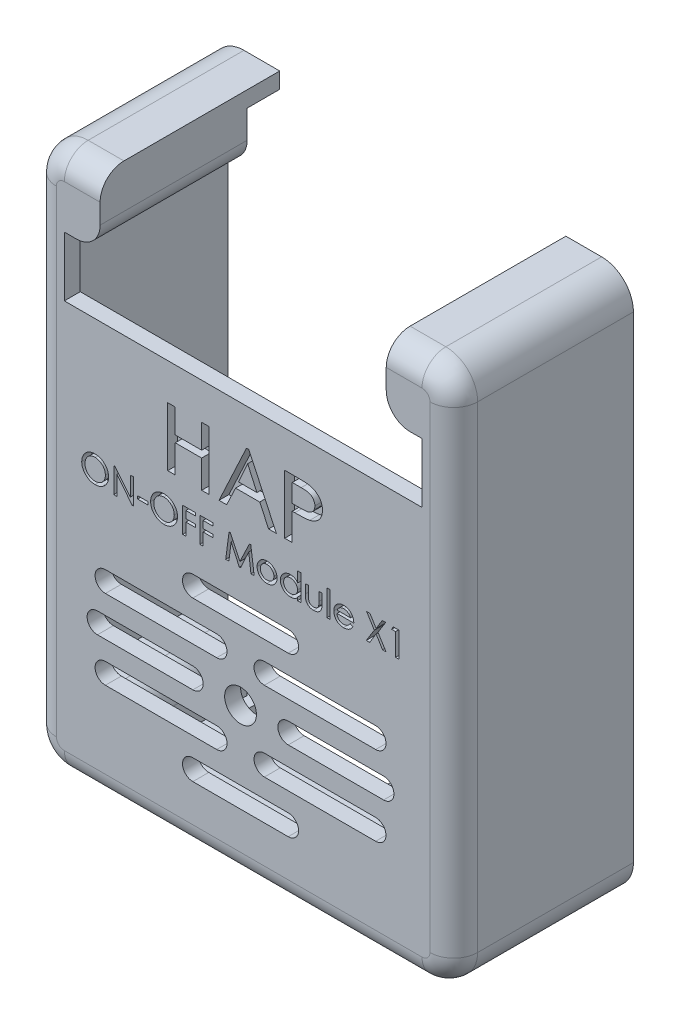
SolidWorks part; units mm, degrees
material "ABS"
ref_plane "Plano frontal" through (0, 0, 0) normal (0, 0, 1) x (1, 0, 0)
ref_plane "Plano superior" through (0, 0, 0) normal (0, 1, 0) x (1, 0, 0)
ref_plane "Plano direito" through (0, 0, 0) normal (1, 0, 0) x (0, 0, -1)
sketch "Esboço1" plane through (0, 0, 0) normal (0, 0, 1) x (1, 0, 0)
  line L1 (-26.5, -34) -> (26.5, -34)
  line L2 (-26.5, -34) -> (-26.5, 34)
  line L3 (-26.5, 34) -> (26.5, 34)
  line L4 (26.5, -34) -> (26.5, 34)
  point P0 (0, 0)
  point P6 (0, 34)
  point P7 (26.5, 0)
  dimension "D1" = 53
  dimension "D2" = 68
  dimension "D3" = 0
  dimension "D4" = 0
extrude "Ressalto-extrusão1" add sketch "Esboço1" along normal blind 22.6
fillet "Filete1" radius 4 4 edges at (-26.5, -34, 11.3) (26.5, -34, 11.3) (-26.5, 34, 11.3) (26.5, 34, 11.3)
fillet "Filete2" radius 3 8 edges at (0, 34, 22.6) (26.5, 0, 22.6) (25.3284, -32.8284, 22.6) (0, -34, 22.6) (-25.3284, -32.8284, 22.6) (-26.5, 0, 22.6) (-25.3284, 32.8284, 22.6) (25.3284, 32.8284, 22.6)
shell "Casca1" thickness 2 removed face at (0, 0, 0)
sketch "Esboço3" plane through (0, 0, 20.6) normal (0, 0, -1) x (-1, 0, 0)
  line L0 (0, 0) -> (0, -34) construction
  line L1 (22.5, -34) -> (-22.5, -34) construction
  line L2 (0, 0) -> (26.5, 0) construction
  line L3 (26.5, 30) -> (26.5, -30) construction
  line L4 (-18, -28.5) -> (-18, -32)
  line L5 (-22.5, -32) -> (22.5, -32) construction
  line L6 (-21, -25.5) -> (-24.5, -25.5)
  line L7 (-24.5, 30) -> (-24.5, -30) construction
  line L8 (-24.5, -30) -> (-24.5, -25.5)
  line L9 (-22.5, -32) -> (-18, -32)
  line L10 (22.5, -32) -> (18, -32)
  line L11 (24.5, -30) -> (24.5, -25.5)
  line L12 (21, -25.5) -> (24.5, -25.5)
  line L13 (18, -28.5) -> (18, -32)
  line L14 (18, 28.5) -> (18, 32)
  line L15 (21, 25.5) -> (24.5, 25.5)
  line L16 (24.5, 30) -> (24.5, 25.5)
  line L17 (22.5, 32) -> (18, 32)
  line L18 (-22.5, 32) -> (-18, 32)
  line L19 (-24.5, 30) -> (-24.5, 25.5)
  line L20 (-21, 25.5) -> (-24.5, 25.5)
  line L21 (-18, 28.5) -> (-18, 32)
  arc A0 (-18, -28.5) -> (-21, -25.5) centre (-21, -28.5) ccw
  arc A4 (-24.5, -30) -> (-22.5, -32) centre (-22.5, -30) ccw
  arc A5 (24.5, -30) -> (22.5, -32) centre (22.5, -30) cw
  arc A6 (18, -28.5) -> (21, -25.5) centre (21, -28.5) cw
  arc A7 (18, 28.5) -> (21, 25.5) centre (21, 28.5) ccw
  arc A8 (24.5, 30) -> (22.5, 32) centre (22.5, 30) ccw
  arc A9 (-24.5, 30) -> (-22.5, 32) centre (-22.5, 30) cw
  arc A10 (-18, 28.5) -> (-21, 25.5) centre (-21, 28.5) cw
  dimension "D1" = 21
  dimension "D2" = 28.5
  dimension "D3" = 6
extrude "Ressalto-extrusão2" add sketch "Esboço3" along normal blind 16.5
sketch "Esboço4" plane through (0, 0, 4.1) normal (0, 0, -1) x (-1, 0, 0)
  line L0 (0, -34) -> (0, 34) construction
  line L1 (22.5, -34) -> (-22.5, -34) construction
  line L2 (-22.5, 34) -> (22.5, 34) construction
  line L3 (-26.5, 0) -> (26.5, 0) construction
  line L4 (-26.5, -30) -> (-26.5, 30) construction
  line L5 (26.5, 30) -> (26.5, -30) construction
  circle A0 centre (-21, -28.5) radius 1
  circle A2 centre (21, -28.5) radius 1
  circle A3 centre (-21, 28.5) radius 1
  circle A4 centre (21, 28.5) radius 1
  dimension "D1" = 2
extrude "Corte-extrusão1" cut sketch "Esboço4" against normal blind 6
sketch "Esboço5" plane through (0, 0, 22.6) normal (0, 0, 1) x (1, 0, 0)
  line L0 (-22.5, 34) -> (22.5, 34) construction
  line L1 (-18, 34) -> (18, 34)
  line L2 (-18, 34) -> (-18, 28.5)
  line L3 (-22.5, 18) -> (22.5, 18)
  line L4 (18, 34) -> (18, 28.5)
  line L5 (21, 25.5) -> (22.5, 25.5)
  line L8 (22.5, 25.5) -> (22.5, 18)
  line L9 (0, 34) -> (0, 0) construction
  line L10 (-22.5, 25.5) -> (-22.5, 18)
  line L11 (-21, 25.5) -> (-22.5, 25.5)
  arc A0 (18, 28.5) -> (21, 25.5) centre (21, 28.5) ccw
  arc A1 (-18, 28.5) -> (-21, 25.5) centre (-21, 28.5) cw
  dimension "D1" = 18
  dimension "D2" = 18
  dimension "D4" = 22.5
extrude "Corte-extrusão2" cut sketch "Esboço5" against normal through all
sketch "Esboço6" plane through (0, 0, 0) normal (0, 0, -1) x (-1, 0, 0)
  line L5 (-18, -32) -> (18, -32) construction
  line L6 (-0.5, -32) -> (16.5, -32)
  line L7 (-0.5, -32) -> (-0.5, -34)
  line L8 (-0.5, -34) -> (16.5, -34)
  line L9 (16.5, -32) -> (16.5, -34)
  line L10 (22.5, -34) -> (-22.5, -34) construction
  line L11 (26.5, 30) -> (26.5, -30) construction
  dimension "D1" = 10
  dimension "D2" = 17
extrude "Corte-extrusão3" cut sketch "Esboço6" against normal blind 6
sketch "Esboço7" plane through (0, -34, 0) normal (0, -1, 0) x (1, 0, 0)
  line L0 (-16.5, 0) -> (-18.5, 0)
  line L1 (-22.5, 0) -> (-16.5, 0) construction
  line L2 (-18.5, 0) -> (-18.5, 8)
  line L3 (-18.5, 8) -> (2.5, 8)
  line L4 (2.5, 8) -> (2.5, 0)
  line L5 (0.5, 0) -> (22.5, 0) construction
  line L6 (2.5, 0) -> (0.5, 0)
  line L7 (0.5, 0) -> (0.5, 6)
  line L8 (0.5, 6) -> (-16.5, 6)
  line L9 (-16.5, 6) -> (-16.5, 0)
  dimension "D1" = 2
  dimension "D2" = 2
  dimension "D3" = 2
extrude "Ressalto-extrusão3" add sketch "Esboço7" along normal blind 4.5
sketch "Esboço8" plane through (0, -38.5, 0) normal (0, -1, 0) x (1, 0, 0)
  line L1 (-18.5, 0) -> (2.5, 0)
  line L2 (-18.5, 0) -> (-18.5, 8)
  line L3 (-18.5, 8) -> (2.5, 8)
  line L4 (2.5, 0) -> (2.5, 8)
extrude "Ressalto-extrusão4" add sketch "Esboço8" along normal blind 1.5
fillet "Filete3" radius 1 8 edges at (-18.5, -37, 8) (-8, -40, 8) (2.5, -37, 8) (2.5, -34, 4) (-18.5, -34, 4) (-8, -34, 8) (2.5, -40, 4) (-18.5, -40, 4)
sketch "Esboço10" plane through (0, 0, 22.6) normal (0, 0, 1) x (1, 0, 0)
  line L0 (-23.5, 6) -> (23.5, 6) construction
  line L1 (-23.5, 30) -> (-23.5, -30) construction
  line L2 (23.5, -30) -> (23.5, 30) construction
  line L3 (-22.5, 18) -> (22.5, 18) construction
  line L4 (-23.5, 0) -> (23.5, 0) construction
  dimension "D1" = 12
  dimension "D2" = 6
sketch "Esboço11" plane through (0, 0, 22.6) normal (0, 0, 1) x (1, 0, 0)
  text T0 "HAP" font "Century Gothic" height in points 28
  text T1 "ON-OFF Module X1" font "Century Gothic" height in points 12
extrude "Corte-extrusão5" cut sketch "Esboço11" against normal blind 1.25
sketch "Esboço15" plane through (0, 0, 22.6) normal (0, 0, 1) x (1, 0, 0)
  line L0 (-18.3326, -13.6963) -> (-6.3326, -13.6963)
  line L1 (-18.3326, -16.2963) -> (-6.3326, -16.2963)
  line L2 (-0.3326, -12.9963) -> (-0.3326, -16.9963) construction
  line L3 (17.6674, -16.2963) -> (5.6674, -16.2963)
  line L4 (17.6674, -13.6963) -> (5.6674, -13.6963)
  circle A0 centre (-0.3326, -14.9963) radius 2
  arc A1 (-6.3326, -16.2963) -> (-6.3326, -13.6963) centre (-6.3326, -14.9963) ccw
  arc A2 (-18.3326, -13.6963) -> (-18.3326, -16.2963) centre (-18.3326, -14.9963) ccw
  arc A3 (17.6674, -13.6963) -> (17.6674, -16.2963) centre (17.6674, -14.9963) cw
  arc A4 (5.6674, -16.2963) -> (5.6674, -13.6963) centre (5.6674, -14.9963) cw
  dimension "D1" = 15
  dimension "D2" = 4
  dimension "D3" = 2.6
  dimension "D4" = 2.6
  dimension "D5" = 6
  dimension "D6" = 0
  dimension "D8" = 0
  dimension "D7" = 12
extrude "Corte-extrusão6" cut sketch "Esboço15" against normal through all
sketch "Esboço16" plane through (0, 0, 22.6) normal (0, 0, 1) x (1, 0, 0)
  line L0 (-19.6326, -14.9963) -> (18.9674, -14.9963) construction
  line L1 (-0.3326, -12.9963) -> (-0.3326, -16.9963) construction
  line L2 (-17.3326, -8.6963) -> (-3.3326, -8.6963)
  line L3 (-17.3326, -11.2963) -> (-3.3326, -11.2963)
  line L4 (16.6674, -11.2963) -> (2.6674, -11.2963)
  line L5 (16.6674, -8.6963) -> (2.6674, -8.6963)
  line L6 (16.6674, -21.2963) -> (2.6674, -21.2963)
  line L7 (16.6674, -18.6963) -> (2.6674, -18.6963)
  line L8 (-17.3326, -18.6963) -> (-3.3326, -18.6963)
  line L9 (-17.3326, -21.2963) -> (-3.3326, -21.2963)
  arc A0 (-18.3326, -13.6963) -> (-18.3326, -16.2963) centre (-18.3326, -14.9963) ccw construction
  arc A1 (17.6674, -16.2963) -> (17.6674, -13.6963) centre (17.6674, -14.9963) ccw construction
  arc A2 (-17.3326, -8.6963) -> (-17.3326, -11.2963) centre (-17.3326, -9.9963) ccw
  arc A3 (-3.3326, -11.2963) -> (-3.3326, -8.6963) centre (-3.3326, -9.9963) ccw
  circle A4 centre (-0.3326, -14.9963) radius 2 construction
  arc A5 (2.6674, -11.2963) -> (2.6674, -8.6963) centre (2.6674, -9.9963) cw
  arc A6 (16.6674, -8.6963) -> (16.6674, -11.2963) centre (16.6674, -9.9963) cw
  arc A7 (16.6674, -21.2963) -> (16.6674, -18.6963) centre (16.6674, -19.9963) ccw
  arc A8 (2.6674, -18.6963) -> (2.6674, -21.2963) centre (2.6674, -19.9963) ccw
  arc A9 (-3.3326, -18.6963) -> (-3.3326, -21.2963) centre (-3.3326, -19.9963) cw
  arc A10 (-17.3326, -21.2963) -> (-17.3326, -18.6963) centre (-17.3326, -19.9963) cw
  dimension "D1" = 2.6
  dimension "D2" = 2.6
  dimension "D3" = 14
  dimension "D4" = 3
  dimension "D5" = 5
extrude "Corte-extrusão7" cut sketch "Esboço16" against normal through all
sketch "Esboço17" plane through (0, 0, 22.6) normal (0, 0, 1) x (1, 0, 0)
  line L0 (-2.3326, -14.9963) -> (1.6674, -14.9963) construction
  line L1 (-6.3326, -6.2963) -> (5.6674, -6.2963)
  line L2 (-6.3326, -3.6963) -> (5.6674, -3.6963)
  line L3 (-6.3326, -26.2963) -> (5.6674, -26.2963)
  line L4 (-6.3326, -23.6963) -> (5.6674, -23.6963)
  circle A0 centre (-0.3326, -14.9963) radius 2 construction
  arc A1 (-6.3326, -3.6963) -> (-6.3326, -6.2963) centre (-6.3326, -4.9963) ccw
  arc A2 (5.6674, -6.2963) -> (5.6674, -3.6963) centre (5.6674, -4.9963) ccw
  arc A3 (-3.3326, -11.2963) -> (-3.3326, -8.6963) centre (-3.3326, -9.9963) ccw construction
  arc A4 (5.6674, -23.6963) -> (5.6674, -26.2963) centre (5.6674, -24.9963) cw
  arc A5 (-6.3326, -26.2963) -> (-6.3326, -23.6963) centre (-6.3326, -24.9963) cw
  dimension "D1" = 5
  dimension "D2" = 2.6
  dimension "D3" = 2.6
  dimension "D4" = 0
  dimension "D5" = 6
  dimension "D6" = 6
extrude "Corte-extrusão8" cut sketch "Esboço17" against normal through all
